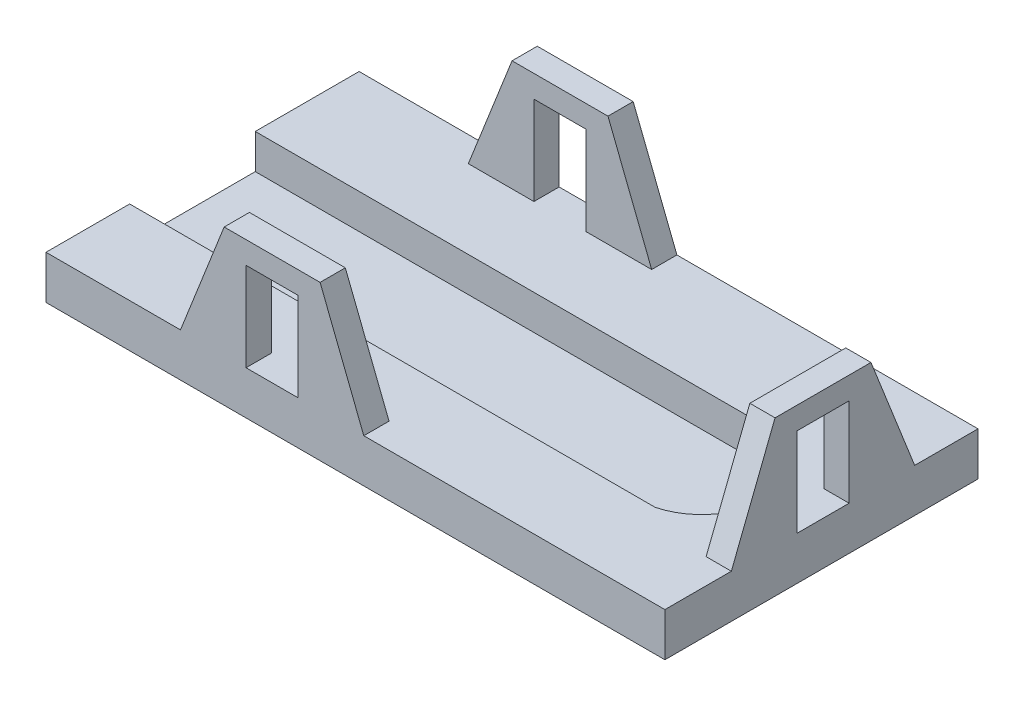
SolidWorks part; units mm, degrees
ref_plane "Front Plane" through (0, 0, 0) normal (0, 0, 1) x (1, 0, 0)
ref_plane "Top Plane" through (0, 0, 0) normal (0, 1, 0) x (1, 0, 0)
ref_plane "Right Plane" through (0, 0, 0) normal (1, 0, 0) x (0, 0, -1)
sketch "Sketch1" plane through (0, 0, 0) normal (0, 1, 0) x (1, 0, 0)
  line L1 (0, 0) -> (35.58, 0)
  line L2 (0, 0) -> (0, 18)
  line L3 (0, 18) -> (35.58, 18)
  line L4 (35.58, 0) -> (35.58, 18)
  dimension "D1" = 35.58
  dimension "D2" = 18
extrude "Boss-Extrude1" add sketch "Sketch1" along normal blind 2.5
sketch "Sketch2" plane through (0, 2.5, 0) normal (0, 1, 0) x (1, 0, 0)
  line L0 (0, 18) -> (0, 0) construction
  line L1 (0, 12.03) -> (30.2037, 12.03)
  line L2 (0, 12.03) -> (0, 4.81)
  line L3 (0, 4.81) -> (30.2037, 4.81)
  line L5 (0, 0) -> (35.58, 0) construction
  arc A0 (30.2037, 12.03) -> (30.2037, 4.81) centre (29.2716, 8.42) cw
  dimension "D3" = 3.7284
  dimension "D1" = 4.81
  dimension "D2" = 7.22
extrude "Cut-Extrude1" cut sketch "Sketch2" against normal blind 2
sketch "Sketch3" plane through (0, 2.5, 0) normal (0, 1, 0) x (1, 0, 0)
  line L0 (35.58, 18) -> (0, 18) construction
  line L1 (7.73, 18) -> (18.27, 18)
  line L2 (7.73, 18) -> (7.73, 16.55)
  line L3 (7.73, 16.55) -> (18.27, 16.55)
  line L4 (18.27, 18) -> (18.27, 16.55)
  line L5 (0, 18) -> (0, 12.03) construction
  dimension "D1" = 1.45
  dimension "D2" = 10.54
  dimension "D3" = 7.73
extrude "Boss-Extrude2" add sketch "Sketch3" along normal blind 6.38
chamfer "Chamfer1" distance 6.38 angle 21.5 2 edges at (18.27, 8.88, -17.275) (7.73, 8.88, -17.275) first distance on face at (18.27, 6.4875, -17.0938) first distance on face at (7.73, 6.4875, -17.4563)
sketch "Sketch4" plane through (0, 0, -16.55) normal (0, 0, 1) x (1, 0, 0)
  line L0 (7.73, 2.5) -> (18.27, 2.5) construction
  line L1 (11.5, 2.5) -> (14.5, 2.5)
  line L2 (11.5, 2.5) -> (11.5, 7.6)
  line L3 (11.5, 7.6) -> (14.5, 7.6)
  line L4 (14.5, 2.5) -> (14.5, 7.6)
  dimension "D1" = 3
  dimension "D2" = 5.1
  dimension "D3" = 3.77
extrude "Cut-Extrude2" cut sketch "Sketch4" against normal blind 6.38
ref_plane "Plane1" through (0, 0, -9) normal (0, 0, 1) x (1, 0, 0)
mirror "Mirror1" about plane through (0, 0, -9) normal (0, 0, 1) of "Chamfer1", "Cut-Extrude2", "Boss-Extrude2"
sketch "Sketch9" plane through (35.58, 0, 0) normal (1, 0, 0) x (0, 0, -1)
sketch "Sketch14" plane through (0, 2.5, 0) normal (0, 1, 0) x (1, 0, 0)
  line L0 (35.58, 0) -> (35.58, 18) construction
  line L1 (35.58, 3.82) -> (34.13, 3.82)
  line L2 (35.58, 3.82) -> (35.58, 14.36)
  line L3 (35.58, 14.36) -> (34.13, 14.36)
  line L4 (34.13, 3.82) -> (34.13, 14.36)
  line L5 (18.27, 0) -> (35.58, 0) construction
  dimension "D1" = 3.82
  dimension "D2" = 10.54
  dimension "D3" = 1.45
extrude "Boss-Extrude5" add sketch "Sketch14" along normal blind 6.38
chamfer "Chamfer4" distance 6.38 angle 21.5 2 edges at (34.855, 8.88, -14.36) (34.855, 8.88, -3.82) first distance on face at (34.855, 5.69, -14.36) first distance on face at (34.855, 5.69, -3.82)
sketch "Sketch15" plane through (34.13, 0, 0) normal (-1, 0, 0) x (0, 0, 1)
  line L0 (-14.36, 2.5) -> (-3.82, 2.5) construction
  line L1 (-10.59, 2.5) -> (-7.59, 2.5)
  line L2 (-10.59, 2.5) -> (-10.59, 7.6)
  line L3 (-10.59, 7.6) -> (-7.59, 7.6)
  line L4 (-7.59, 2.5) -> (-7.59, 7.6)
  dimension "D1" = 5.1
  dimension "D2" = 3
  dimension "D3" = 3.77
extrude "Cut-Extrude4" cut sketch "Sketch15" against normal blind 6.38
